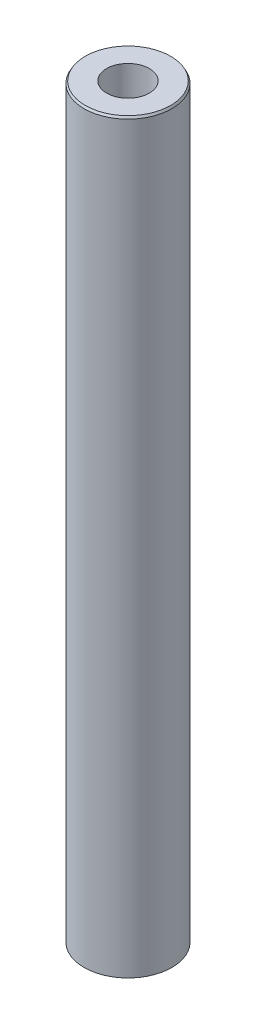
SolidWorks part; units mm, degrees
ref_plane "Front Plane" through (0, 0, 0) normal (0, 0, 1) x (1, 0, 0)
ref_plane "Top Plane" through (0, 0, 0) normal (0, 1, 0) x (1, 0, 0)
ref_plane "Right Plane" through (0, 0, 0) normal (1, 0, 0) x (0, 0, -1)
sketch "Sketch1" plane through (0, 0, 0) normal (0, 1, 0) x (1, 0, 0)
  circle A0 centre (0, 0) radius 12.5
  dimension "SHAFT_OD" = 25
extrude "Boss-Extrude1" add sketch "Sketch1" along normal blind 212.6987
sketch "Sketch2" plane through (0, 0, 0) normal (0, 1, 0) x (1, 0, 0)
  circle A0 centre (0, 0) radius 6.073
  dimension "BORE_D" = 12.1459
extrude "Cut-Extrude1" cut sketch "Sketch2" along normal through all
chamfer "Chamfer1" distance 0.6149 angle 30 2 edges at (0, 212.6987, 12.5) (0, 0, 12.5) first distance on face at (0, 212.6987, 12.5) first distance on face at (0, 0, 6.073)
